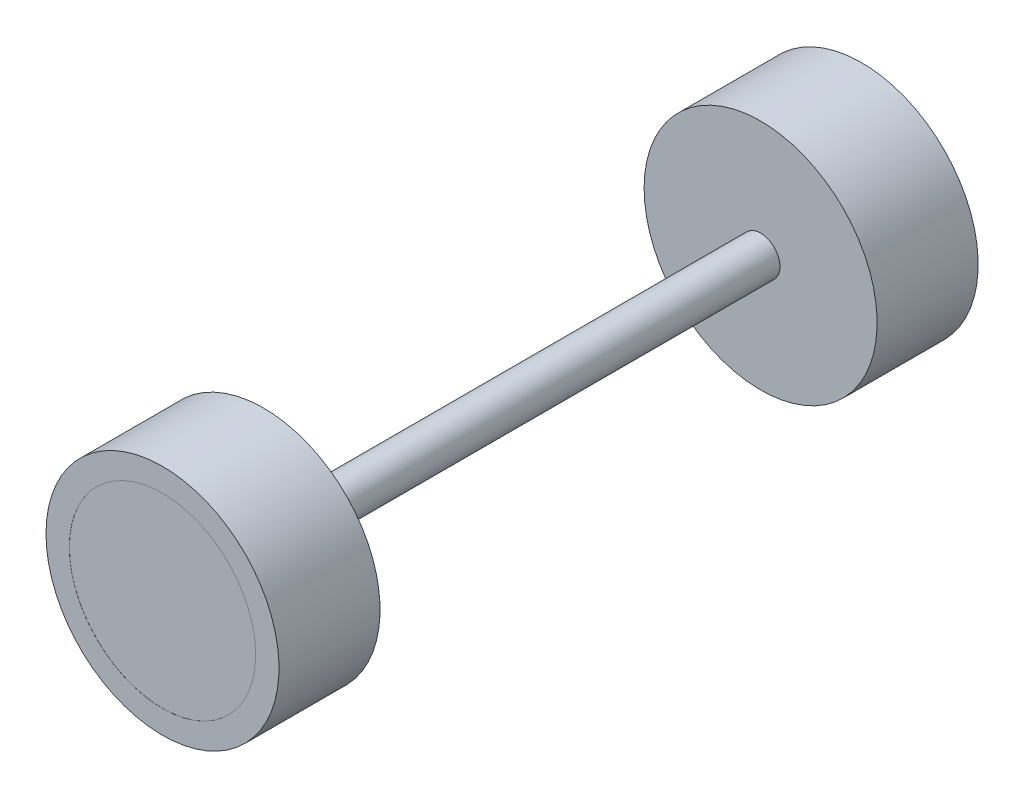
SolidWorks part; units mm, degrees
ref_plane "Alzado" through (0, 0, 0) normal (0, 0, 1) x (1, 0, 0)
ref_plane "Planta" through (0, 0, 0) normal (0, 1, 0) x (1, 0, 0)
ref_plane "Vista lateral" through (0, 0, 0) normal (1, 0, 0) x (0, 0, -1)
sketch "Croquis1" plane through (0, 0, 0) normal (0, 0, 1) x (1, 0, 0)
  circle A0 centre (0, 0) radius 15
  dimension "D1" = 30
extrude "Saliente-Extruir1" add sketch "Croquis1" along normal blind 13
sketch "Croquis2" plane through (0, 0, 13) normal (0, 0, 1) x (1, 0, 0)
  circle A0 centre (0, 0) radius 2.5
  dimension "D1" = 5
extrude "Saliente-Extruir2" add sketch "Croquis2" along normal blind 32
split "Partir1" bodies to split 102 resulting bodies 103 104 split by face at (2.5, 0, 13)
ref_plane "Plano1" through (0, 0, 45) normal (0, 0, 1) x (1, 0, 0)
mirror "Simetría1" about plane through (0, 0, 45) normal (0, 0, 1) of "Saliente-Extruir1", "Saliente-Extruir2"
sketch "Croquis3" plane through (0, 0, 90) normal (0, 0, 1) x (1, 0, 0)
  circle A0 centre (0, 0) radius 12
  circle A1 centre (0, 0) radius 15 construction
  circle A2 centre (0, 0) radius 15
  dimension "D1" = 3
extrude "Saliente-Extruir3" add sketch "Croquis3" along normal blind 0.01
sketch "Croquis4" plane through (0, 0, 0) normal (0, 0, -1) x (-1, 0, 0)
  circle A0 centre (0, 0) radius 12
  circle A1 centre (0, 0) radius 15 construction
  circle A2 centre (0, 0) radius 15
  dimension "D1" = 3
extrude "Saliente-Extruir4" add sketch "Croquis4" along normal blind 0.01
